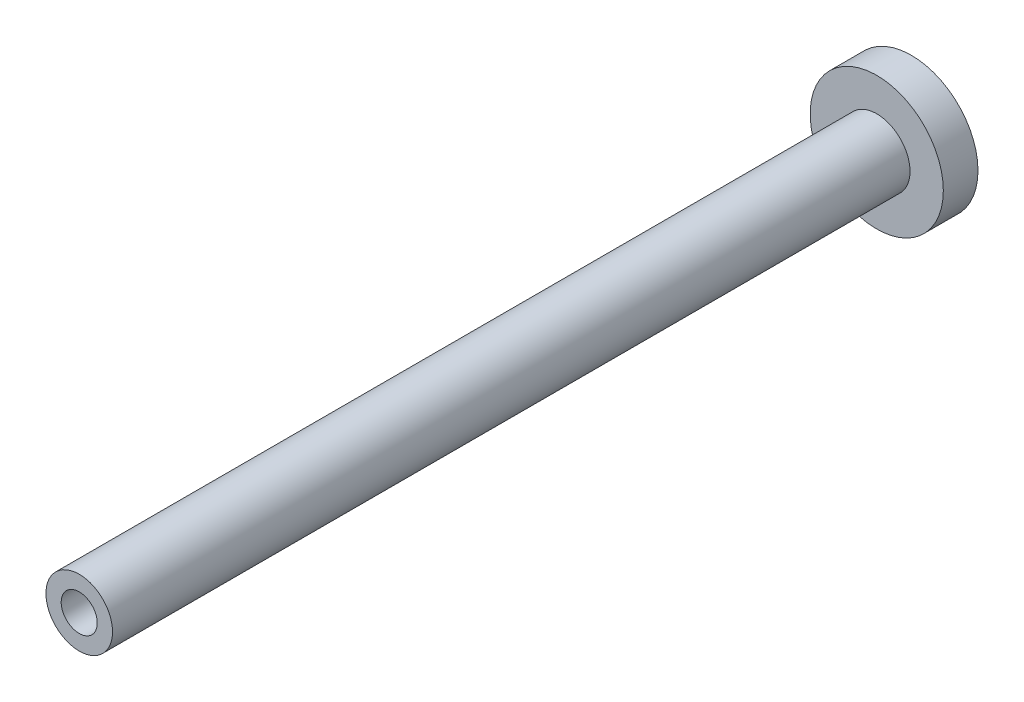
SolidWorks part; units mm, degrees
ref_plane "Front Plane" through (0, 0, 0) normal (0, 0, 1) x (1, 0, 0)
ref_plane "Top Plane" through (0, 0, 0) normal (0, 1, 0) x (1, 0, 0)
ref_plane "Right Plane" through (0, 0, 0) normal (1, 0, 0) x (0, 0, -1)
sketch "Sketch1" plane through (0, 0, 0) normal (0, 0, 1) x (1, 0, 0)
  line L0 (0, -4.8) -> (0, 4.8) construction
  circle A0 centre (0, 0) radius 4.8
  point P6 (0, 0)
  dimension "D2" = 9.6
extrude "Boss-Extrude1" add sketch "Sketch1" along normal blind 60
sketch "Sketch6" plane through (0, 0, 0) normal (0, 0, -1) x (-1, 0, 0)
  circle A0 centre (0, 0) radius 1.25
  dimension "D1" = 2.5
extrude "Boss-Extrude2" add sketch "Sketch6" along normal blind 2.5
sketch "Sketch7" plane through (0, 0, 60) normal (0, 0, 1) x (1, 0, 0)
  circle A0 centre (0, 0) radius 1.3
  dimension "D1" = 2.6
extrude "Cut-Extrude1" cut sketch "Sketch7" against normal blind 2.5
sketch "Sketch9" plane through (0, 0, 60) normal (0, 0, 1) x (1, 0, 0)
  circle A0 centre (0, 0) radius 2.4
  dimension "D1" = 4.8
extrude "Cut-Extrude2" cut sketch "Sketch9" against normal blind 57.5 flip side to cut contours A0
